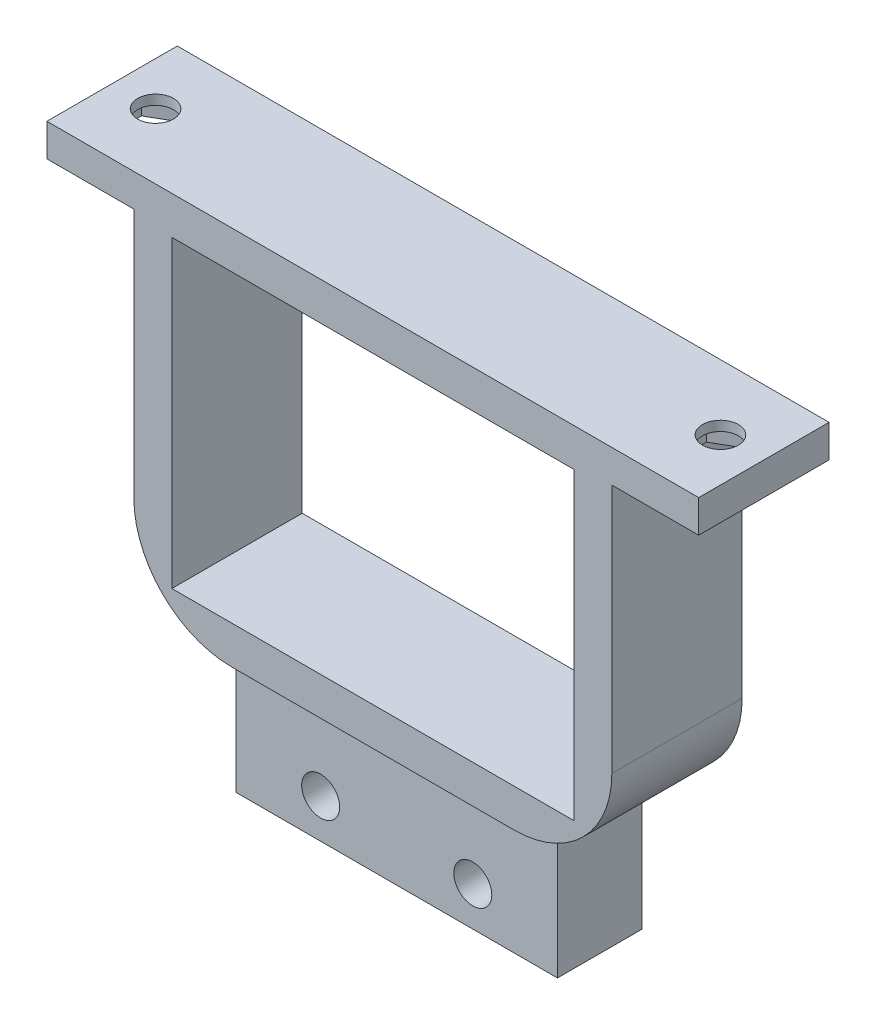
SolidWorks part; units mm, degrees
ref_plane "Front Plane" through (0, 0, 0) normal (0, 0, 1) x (1, 0, 0)
ref_plane "Top Plane" through (0, 0, 0) normal (0, 1, 0) x (1, 0, 0)
ref_plane "Right Plane" through (0, 0, 0) normal (1, 0, 0) x (0, 0, -1)
sketch "Sketch1" plane through (0, 0, 0) normal (0, 0, 1) x (1, 0, 0)
  line L0 (-44, 0) -> (-36.8, -12) construction
  line L1 (0, 0) -> (-44, 0)
  line L2 (0, 0) -> (0, 35)
  line L3 (0, 35) -> (-44, 35)
  line L4 (-44, 0) -> (-44, 35)
  line L5 (-36.8, -3) -> (-7.2, -3)
  line L6 (-36.8, -3) -> (-36.8, -12)
  line L7 (-36.8, -12) -> (-7.2, -12)
  line L8 (-7.2, -3) -> (-7.2, -12)
  line L9 (-7.2, -12) -> (0, 0) construction
  line L10 (-36.8, -8.4) -> (-7.2, -8.4) construction
  line L11 (-3.5, 17.5) -> (-40.5, 17.5) construction
  line L12 (-3.5, 31.5) -> (-40.5, 31.5)
  line L13 (-3.5, 31.5) -> (-3.5, 3.5)
  line L14 (-3.5, 3.5) -> (-40.5, 3.5)
  line L15 (-40.5, 31.5) -> (-40.5, 3.5)
  line L16 (-22, 35) -> (-22, 0) construction
  line L17 (0, 35) -> (8, 35)
  line L18 (8, 35) -> (8, 32)
  line L19 (8, 32) -> (0, 32)
  line L20 (-44, 35) -> (-52, 35)
  line L21 (-52, 35) -> (-52, 32)
  line L22 (-52, 32) -> (-44, 32)
  line L23 (-36.8, -3) -> (-36.8, 0)
  line L24 (-7.2, -3) -> (-7.2, 0)
  circle A0 centre (-29, -8.4) radius 1.75
  circle A1 centre (-15, -8.4) radius 1.75
  point P11 (-29, -8.4)
  point P12 (-15, -8.4)
  point P13 (-22, -8.4)
  point P22 (-22, 17.5)
  dimension "D8" = 3.5
  dimension "D9" = 3.5
  dimension "D1" = 35
  dimension "D2" = 44
  dimension "D3" = 9
  dimension "D4" = 29.6
  dimension "D5" = 5.4
  dimension "D6" = 7
  dimension "D7" = 7
  dimension "D10" = 37
  dimension "D11" = 28
  dimension "D12" = 3
  dimension "D13" = 8
  dimension "D14" = 3
  dimension "D15" = 8
  dimension "D16" = 3
extrude "Boss-Extrude1" add sketch "Sketch1" along normal blind 7.8 contours L4 L1 L2 L3 | L8 L1 L6 L7 A1 A0 | L19 L18 L17 L2 | L21 L22 L4 L20 | L5 L24 L1 L23 region at (-3.6, 0.5622, 0) region at (-22, -1.5, 0) region at (4, 33.5, 0) region at (-22, -7.4299, 0) region at (-48, 33.5, 0)
extrude "Boss-Extrude2" add sketch "Sketch1<3>" along normal blind 10 and the other way blind 2 contours L4 L1 L2 L3 L15 L12 L13 L14 | L19 L18 L17 L2 | L21 L22 L4 L20 region at (-3.6, 0.5622, 0) region at (4, 33.5, 0) region at (-48, 33.5, 0)
sketch "Sketch1<3>" plane through (0, 0, 0) normal (0, 0, 1) x (1, 0, 0) same geometry as "Sketch1"
fillet "Fillet1" radius 9 2 edges at (0, 0, 4) (-44, 0, 4)
sketch "Sketch2" plane through (0, 32, 0) normal (0, -1, 0) x (1, 0, 0)
  line L0 (-52, 4) -> (-44, 4) construction
  line L1 (-52, 10) -> (-52, -2) construction
  line L2 (-44, 10) -> (-44, -2) construction
  line L3 (8, 4) -> (0, 4) construction
  line L4 (-44.925, 5.7754) -> (-48, 7.5507)
  line L5 (-48, 7.5507) -> (-51.075, 5.7754)
  line L6 (-51.075, 5.7754) -> (-51.075, 2.2246)
  line L7 (-51.075, 2.2246) -> (-48, 0.4493)
  line L8 (-48, 0.4493) -> (-44.925, 2.2246)
  line L9 (-44.925, 2.2246) -> (-44.925, 5.7754)
  line L10 (8, 10) -> (8, -2) construction
  line L11 (0, 10) -> (0, -2) construction
  line L13 (4, 0.4493) -> (7.075, 2.2246)
  line L14 (7.075, 2.2246) -> (7.075, 5.7754)
  line L15 (7.075, 5.7754) -> (4, 7.5507)
  line L16 (4, 7.5507) -> (0.925, 5.7754)
  line L17 (0.925, 5.7754) -> (0.925, 2.2246)
  line L18 (0.925, 2.2246) -> (4, 0.4493)
  circle A0 centre (-48, 4) radius 3.075 construction
  circle A1 centre (4, 4) radius 3.075 construction
  point P6 (-48, 4)
  point P21 (4, 4)
  dimension "D1" = 6.15
  dimension "D2" = 6.15
extrude "Cut-Extrude1" cut sketch "Sketch2" against normal blind 2.1 contours L8 L9 L4 L5 L6 L7 | L17 L18 L13 L14 L15 L16 region at (-48, 32, 4) region at (4, 32, 4)
hole_wizard "Hole1" positions "3DSketch1" profile "Sketch3" legacy end condition through all
sketch3d "3DSketch1"
  point P0 (-48, 32, 4)
  point P3 (4, 32, 4)
sketch "Sketch3" plane through (-48, 32, 4) normal (1, 0, 0) x (0, 0, -1)
  line L0 (0, 0) -> (0, 3)
  line L1 (0, 3) -> (1.65, 3)
  line L2 (1.65, 3) -> (1.65, 0)
  line L3 (1.65, 0) -> (0, 0)
  line L4 (0, 110) -> (0, -10) construction
  dimension "Diameter" = 3.3
  dimension "Depth" = 3
